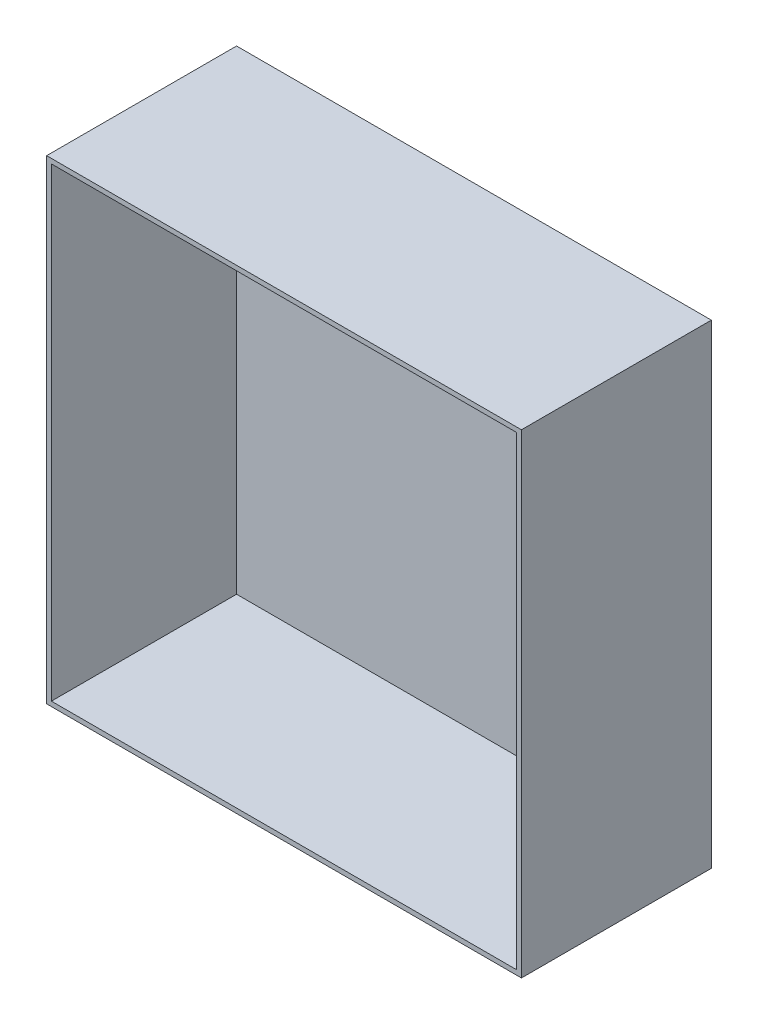
SolidWorks part; units mm, degrees
ref_plane "Front Plane" through (0, 0, 0) normal (0, 0, 1) x (1, 0, 0)
ref_plane "Top Plane" through (0, 0, 0) normal (0, 1, 0) x (1, 0, 0)
ref_plane "Right Plane" through (0, 0, 0) normal (1, 0, 0) x (0, 0, -1)
sketch "Sketch1" plane through (0, 0, 0) normal (0, 1, 0) x (1, 0, 0)
  line L0 (-127, 50.8) -> (127, -50.8) construction
  line L1 (-127, 50.8) -> (127, 50.8)
  line L2 (-127, 50.8) -> (-127, -50.8)
  line L3 (-127, -50.8) -> (127, -50.8)
  line L4 (127, 50.8) -> (127, -50.8)
  dimension "D1" = 254
  dimension "D2" = 101.6
extrude "Boss-Extrude1" add sketch "Sketch1" along normal mid plane 254
shell "Shell1" thickness 2.54 removed face at (0, 0, 50.8)
